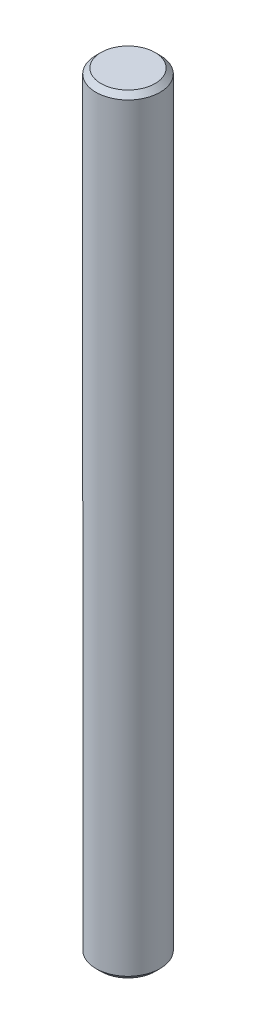
SolidWorks part; units mm, degrees
ref_plane "Front Plane" through (0, 0, 0) normal (0, 0, 1) x (1, 0, 0)
ref_plane "Top Plane" through (0, 0, 0) normal (0, 1, 0) x (1, 0, 0)
ref_plane "Right Plane" through (0, 0, 0) normal (1, 0, 0) x (0, 0, -1)
sketch "Bar face" plane through (0, 0, 0) normal (0, 1, 0) x (1, 0, 0)
  circle A0 centre (0, 0) radius 3.175
  dimension "D1" = 6.35
extrude "Bar extrude" add sketch "Bar face" along normal blind 76.2
chamfer "Chamfer2" distance 0.5 2 edges at (0, 76.2, 3.175) (0, 0, 3.175) tangent propagation no
